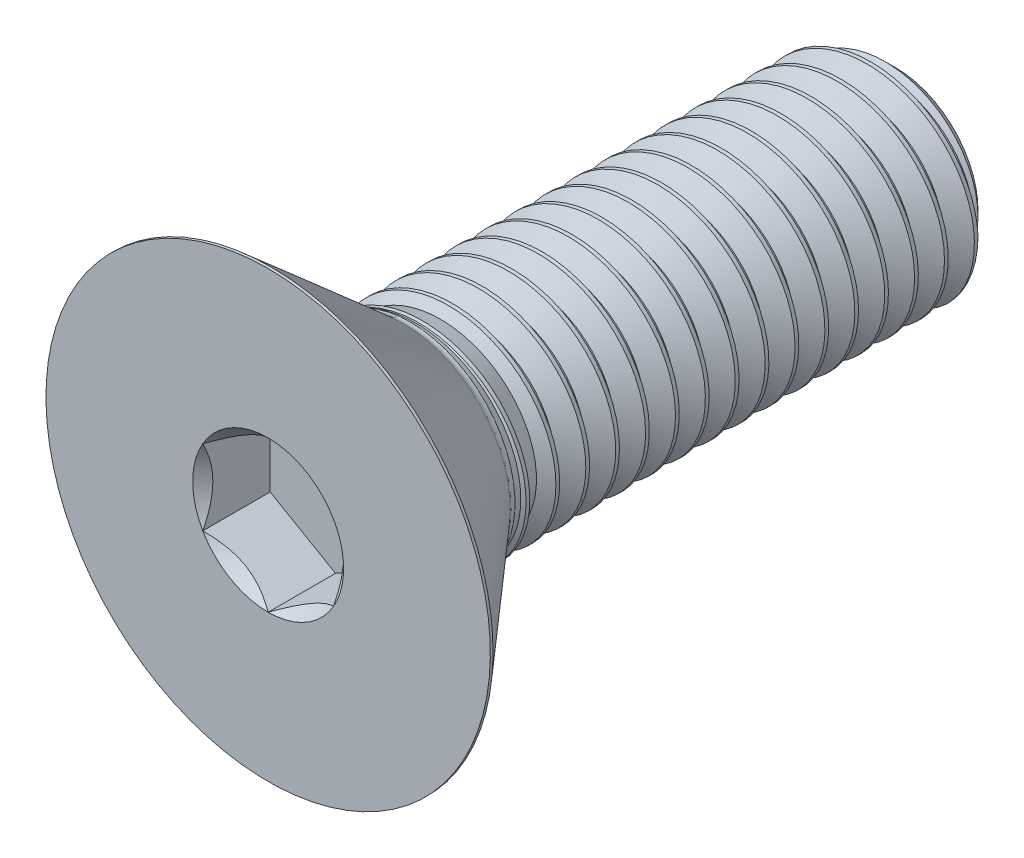
SolidWorks part; units mm, degrees
ref_plane "Front Plane" through (0, 0, 0) normal (0, 0, 1) x (1, 0, 0)
ref_plane "Top Plane" through (0, 0, 0) normal (0, 1, 0) x (1, 0, 0)
ref_plane "Right Plane" through (0, 0, 0) normal (1, 0, 0) x (0, 0, -1)
sketch "Sketch1" plane through (0, 0, 0) normal (1, 0, 0) x (0, 0, -1)
  line L0 (-9.525, 0) -> (9.525, 0) construction
  line L1 (-9.525, 0) -> (-9.525, 6.7437)
  line L2 (-9.525, 6.7437) -> (-9.4432, 6.7437)
  line L3 (-9.4432, 6.7437) -> (-5.4356, 3.2599)
  line L4 (-9.4432, -6.7437) -> (-5.4356, -3.2599)
  line L5 (9.525, 0) -> (9.525, 3.175)
  line L6 (9.525, 3.175) -> (-5.4356, 3.175)
  line L7 (8.8446, 3.175) -> (9.525, 2.4946)
  line L8 (9.4683, 3.2732) -> (9.9219, 2.4876) construction
  line L9 (9.9219, 2.4876) -> (10.3754, 3.2732) construction
  line L10 (10.3754, 3.2732) -> (9.4683, 3.2732) construction
  line L11 (9.4967, 3.2241) -> (10.3471, 3.2241)
  line L12 (10.3471, 3.2241) -> (9.9786, 2.5858)
  line L13 (9.9786, 2.5858) -> (9.8652, 2.5858)
  line L14 (9.8652, 2.5858) -> (9.4967, 3.2241)
  line L15 (9.9219, 2.5858) -> (9.9219, 2.4876) construction
  line L16 (9.525, 3.175) -> (10.3188, 3.175) construction
  line L17 (9.9219, 3.2732) -> (9.9219, 3.175) construction
  line L18 (9.525, -3.175) -> (-5.4356, -3.175)
  arc A0 (-5.4356, 3.2599) -> (-5.2084, 3.175) centre (-5.2084, 3.5213) ccw
  point P2 (0, 0)
  point P23 (-7.4803, 0)
  point P27 (9.9219, 3.2241)
  point P30 (8.1643, -3.175)
  point P31 (-5.4356, 6.7437)
  point P34 (-9.4432, -6.7437)
  dimension "Length" = 19.05
  dimension "Head Height" = 4.0894
  dimension "Head Diameter" = 13.4874
  dimension "Countersink Angle" = 82
  dimension "Screw Size Decimal Equivalent" = 6.35
  dimension "Pitch" = 0.9071
  dimension "D4" = 0.1134
  dimension "D3" = 45
  dimension "D5" = 0.6804
  dimension "D6" = 2.0447
  dimension "D1" = 1.3607
  dimension "D7" = 0.0818
sketch "Sketch8" plane through (0, 0, 0) normal (0, 0, 1) x (1, 0, 0)
  line L1 (0, 2.2914) -> (-1.9844, 1.1457)
  line L2 (-1.9844, 1.1457) -> (-1.9844, -1.1457)
  line L3 (-1.9844, -1.1457) -> (0, -2.2914)
  line L4 (0, -2.2914) -> (1.9844, -1.1457)
  line L5 (1.9844, -1.1457) -> (1.9844, 1.1457)
  line L6 (1.9844, 1.1457) -> (0, 2.2914)
  circle A0 centre (0, 0) radius 1.9844 construction
  dimension "Drive Size" = 3.9688
sketch "Sketch2" plane through (0, 0, 0) normal (1, 0, 0) x (0, 0, -1)
  line L0 (-9.4432, 6.7437) -> (-5.4356, 3.2599) construction
  line L1 (-9.525, 0) -> (-9.525, 6.7437) construction
  line L2 (-9.4432, 6.7437) -> (-5.4356, 3.2599)
  line L3 (-9.525, 0) -> (-9.525, 6.7437)
  line L4 (-9.525, 6.7437) -> (-9.4432, 6.7437) construction
  line L5 (-9.525, 6.7437) -> (-9.4432, 6.7437)
  line L6 (-5.2084, 3.175) -> (8.8446, 3.175)
  line L7 (8.8446, 3.175) -> (9.525, 2.4946)
  line L8 (9.525, 2.4946) -> (9.525, 0)
  line L9 (9.525, 0) -> (-9.525, 0)
  arc A0 (-5.4356, 3.2599) -> (-5.2084, 3.175) centre (-5.2084, 3.5213) ccw construction
  arc A1 (-5.4356, 3.2599) -> (-5.2084, 3.175) centre (-5.2084, 3.5213) ccw
revolve "Revolve1" add sketch "Sketch2" angle 360 about L9
sketch "Sketch9" plane through (0, 0, 9.525) normal (0, 0, 1) x (1, 0, 0)
  line L0 (1.9844, -1.1457) -> (1.9844, 1.1457) construction
  line L1 (0, -2.2914) -> (1.9844, -1.1457) construction
  line L2 (-1.9844, -1.1457) -> (0, -2.2914) construction
  line L3 (-1.9844, 1.1457) -> (-1.9844, -1.1457) construction
  line L4 (0, 2.2914) -> (-1.9844, 1.1457) construction
  line L5 (1.9844, 1.1457) -> (0, 2.2914) construction
  line L6 (1.9844, -1.1457) -> (1.9844, 1.1457)
  line L7 (0, -2.2914) -> (1.9844, -1.1457)
  line L8 (-1.9844, -1.1457) -> (0, -2.2914)
  line L9 (-1.9844, 1.1457) -> (-1.9844, -1.1457)
  line L10 (0, 2.2914) -> (-1.9844, 1.1457)
  line L11 (1.9844, 1.1457) -> (0, 2.2914)
sketch "Sketch10" plane through (0, 0, 9.525) normal (0, 0, 1) x (1, 0, 0)
  circle A0 centre (0, 0) radius 2.2914
extrude "Cut-Extrude2" cut sketch "Sketch10" against normal up to vertex (2.0447 mm away) draft 45 up to point (0, 0, 7.4803)
extrude "Cut-Extrude1" cut sketch "Sketch9" against normal up to vertex (2.0447 mm away) up to point (0, 0, 7.4803)
ref_plane "Plane1" through (0, 0, 5.2084) normal (0, 0, 1) x (1, 0, 0)
split "Split1" trim tools "Plane1" bodies to split 111 resulting bodies 105 106
sketch "Sketch3" plane through (0, 0, -9.525) normal (0, 0, -1) x (-1, 0, 0)
  circle A0 centre (0, 0) radius 3.175 construction
  circle A1 centre (0, 0) radius 3.175
curve "Helix/Spiral1" pitch 0.9071 height 19.05 turns 21
sketch "Sketch4" plane through (0, 0, 0) normal (1, 0, 0) x (0, 0, -1)
  line L0 (9.4967, 3.2241) -> (10.3471, 3.2241) construction
  line L1 (9.8652, 2.5858) -> (9.4967, 3.2241) construction
  line L2 (9.9786, 2.5858) -> (9.8652, 2.5858) construction
  line L3 (10.3471, 3.2241) -> (9.9786, 2.5858) construction
  line L4 (9.4967, 3.2241) -> (10.3471, 3.2241)
  line L5 (9.8652, 2.5858) -> (9.4967, 3.2241)
  line L6 (9.9786, 2.5858) -> (9.8652, 2.5858)
  line L7 (10.3471, 3.2241) -> (9.9786, 2.5858)
sweep "Cut-Sweep1" cut profiles "Sketch4" path "Helix/Spiral1" align with end faces yes
sketch "Sketch7" plane through (0, 0, 5.2084) normal (0, 0, 1) x (1, 0, 0)
  circle A0 centre (0, 0) radius 3.175
extrude "Boss-Extrude2" add sketch "Sketch7" against normal up to next (14.7334 mm away) draft 20
equation "\"D4@Sketch1\" = \"Pitch@Sketch1\" / 8"
equation "\"D5@Sketch1\"=\"Pitch@Sketch1\"*0.75"
equation "\"D4@Helix/Spiral1\"=\"Pitch@Sketch1\""
equation "\"D3@Helix/Spiral1\"=\"Length@Sketch1\""
equation "\"D6@Sketch1\"=\"Head Height@Sketch1\"/2"
equation "\"D1@Sketch1\"=\"Pitch@Sketch1\"*1.5"
equation "\"D7@Sketch1\"=\"Head Height@Sketch1\"*0.02"
